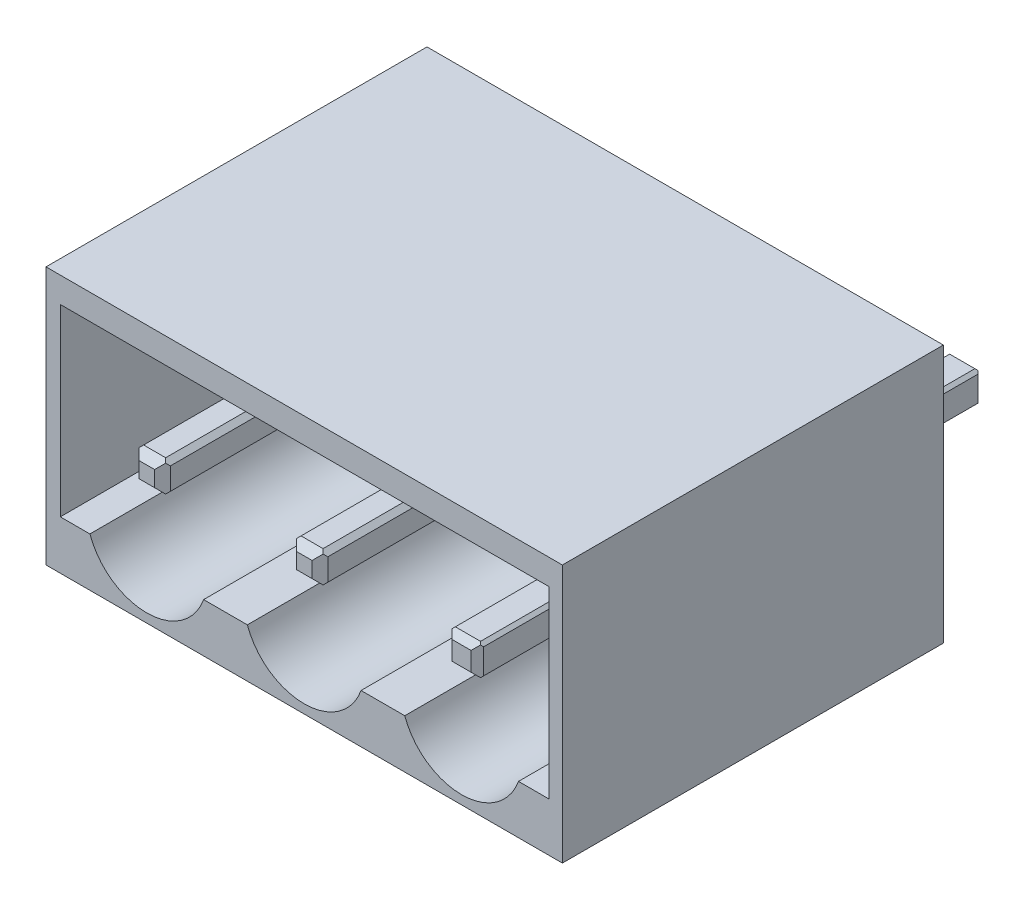
SolidWorks part; units mm, degrees
ref_plane "Спереди" through (0, 0, 0) normal (0, 0, 1) x (1, 0, 0)
ref_plane "Сверху" through (0, 0, 0) normal (0, 1, 0) x (1, 0, 0)
ref_plane "Справа" through (0, 0, 0) normal (1, 0, 0) x (0, 0, -1)
sketch "Эскиз1" plane through (0, 0, 0) normal (0, 0, 1) x (1, 0, 0)
  line L1 (-8.2, 4.1) -> (8.2, 4.1)
  line L2 (-8.2, 4.1) -> (-8.2, -4.1)
  line L3 (-8.2, -4.1) -> (8.2, -4.1)
  line L4 (8.2, 4.1) -> (8.2, -4.1)
  line L5 (-8.2, 4.1) -> (8.2, -4.1) construction
  line L6 (-8.2, -4.1) -> (8.2, 4.1) construction
  point P0 (0, 0)
  dimension "D1" = 8.2
  dimension "D2" = 16.4
extrude "Бобышка-Вытянуть1" add sketch "Эскиз1" along normal blind 12.1
sketch "Эскиз4" plane through (0, 0, 12.1) normal (0, 0, 1) x (1, 0, 0)
  circle A0 centre (-5, 0) radius 1.25
  circle A1 centre (0, 0) radius 1.25
  circle A2 centre (5, 0) radius 1.25
  dimension "D1" = 2.5
  dimension "D2" = 5
  dimension "D3" = 2
  dimension "D4" = 2
extrude "Вырез-Вытянуть3" cut sketch "Эскиз4" against normal blind 8
sketch "Эскиз5" plane through (0, 0, 12.1) normal (0, 0, 1) x (1, 0, 0)
  line L0 (-7.7456, 0) -> (-7.7456, 3.2929)
  line L1 (-7.7456, 3.2929) -> (2.7785, 3.2929)
  line L4 (-7.7456, -2.549) -> (-7.7456, 0)
  line L5 (1.8058, -2.549) -> (3.1942, -2.549)
  line L6 (-6.8058, -2.549) -> (-7.7456, -2.549)
  line L7 (-3.1942, -2.549) -> (-1.8058, -2.549)
  line L9 (6.8058, -2.549) -> (7.7785, -2.549)
  line L10 (7.7785, 3.2929) -> (7.7785, -2.549)
  line L11 (2.7785, 3.2929) -> (7.7785, 3.2929)
  line L13 (1.8058, -2.549) -> (3.1942, -2.549) [skipped]
  arc A1 (3.1942, -2.549) -> (6.8058, -2.549) centre (5, -1.9) ccw
  arc A5 (-6.8058, -2.549) -> (-3.1942, -2.549) centre (-5, -1.9) ccw
  arc A6 (-1.8058, -2.549) -> (1.8058, -2.549) centre (0, -1.9) ccw
  dimension "D1" = 3.2
  dimension "D2" = 2.2
  dimension "D3" = 2
  dimension "D4" = 2
extrude "Вырез-Вытянуть4" cut sketch "Эскиз5" against normal blind 7.8
sketch "Эскиз7" plane through (0, 0, 4.1) normal (0, 0, 1) x (1, 0, 0)
  line L0 (-0.5, 0.5) -> (0.5, 0.5)
  line L1 (-5.5, 0.5) -> (-4.5, 0.5)
  line L2 (-5.5, 0.5) -> (-5.5, -0.5)
  line L3 (-5.5, -0.5) -> (-4.5, -0.5)
  line L4 (-4.5, 0.5) -> (-4.5, -0.5)
  line L5 (-5.5, 0.5) -> (-4.5, -0.5) construction
  line L6 (-5.5, -0.5) -> (-4.5, 0.5) construction
  line L7 (-0.5, 0.5) -> (-0.5, -0.5)
  line L8 (-0.5, -0.5) -> (0.5, -0.5)
  line L9 (0.5, 0.5) -> (0.5, -0.5)
  line L10 (-0.5, 0.5) -> (0.5, -0.5) construction
  line L11 (-0.5, -0.5) -> (0.5, 0.5) construction
  line L12 (4.5, 0.5) -> (5.5, 0.5)
  line L13 (4.5, 0.5) -> (4.5, -0.5)
  line L14 (4.5, -0.5) -> (5.5, -0.5)
  line L15 (5.5, 0.5) -> (5.5, -0.5)
  line L16 (4.5, 0.5) -> (5.5, -0.5) construction
  line L17 (4.5, -0.5) -> (5.5, 0.5) construction
  point P0 (-5, 0)
  point P7 (0, 0)
  point P12 (5, 0)
  dimension "D1" = 1
  dimension "D2" = 1
  dimension "D3" = 2
  dimension "D4" = 2
extrude "Бобышка-Вытянуть2" add sketch "Эскиз7" along normal blind 8
chamfer "Фаска1" distance 0.15 angle 45 8 edges at (-0.5, -0.5, 8.1) (-0.5, 0.5, 8.1) (0.5, 0.5, 8.1) (0.5, -0.5, 8.1) (-4.5, -0.5, 8.1) (-4.5, 0.5, 8.1) (-5.5, -0.5, 8.1) (-5.5, 0.5, 8.1)
chamfer "Фаска2" distance 0.25 angle 45 8 edges at (-0.5, 0, 12.1) (0, 0.5, 12.1) (0.5, 0, 12.1) (0, -0.5, 12.1) (-4.5, 0, 12.1) (-5, -0.5, 12.1) (-5.5, 0, 12.1) (-5, 0.5, 12.1)
sketch "Эскиз8" plane through (0, -4.1, 0) normal (0, 0, 1) x (-1, 0, 0)
  line L0 (0.5, -4.25) -> (-0.5, -4.25)
  line L1 (5.5, -4.25) -> (4.5, -4.25)
  line L2 (5.5, -4.25) -> (5.5, -3.25)
  line L3 (5.5, -3.25) -> (4.5, -3.25)
  line L4 (4.5, -4.25) -> (4.5, -3.25)
  line L5 (5.5, -4.25) -> (4.5, -3.25) construction
  line L6 (5.5, -3.25) -> (4.5, -4.25) construction
  line L7 (0.5, -4.25) -> (0.5, -3.25)
  line L8 (0.5, -3.25) -> (-0.5, -3.25)
  line L9 (-0.5, -4.25) -> (-0.5, -3.25)
  line L10 (0.5, -4.25) -> (-0.5, -3.25) construction
  line L11 (0.5, -3.25) -> (-0.5, -4.25) construction
  line L12 (-4.5, -4.25) -> (-5.5, -4.25)
  line L13 (-4.5, -4.25) -> (-4.5, -3.25)
  line L14 (-4.5, -3.25) -> (-5.5, -3.25)
  line L15 (-5.5, -4.25) -> (-5.5, -3.25)
  line L16 (-4.5, -4.25) -> (-5.5, -3.25) construction
  line L17 (-4.5, -3.25) -> (-5.5, -4.25) construction
  point P0 (5, -3.75)
  point P7 (0, -3.75)
  point P12 (-5, -3.75)
  dimension "D1" = 1
  dimension "D2" = 1
  dimension "D3" = 3.2
  dimension "D4" = 4.45
  dimension "D5" = 2
  dimension "D6" = 2
extrude "Бобышка-Вытянуть3" add sketch "Эскиз8" against normal blind 4
chamfer "Фаска6" distance 0.1 angle 45 4 edges at (4.5, -0.5, 8.1) (5.5, -0.5, 8.1) (5.5, 0.5, 8.1) (4.5, 0.5, 8.1)
chamfer "Фаска7" distance 0.2 angle 45 4 edges at (5.5, 0, 12.1) (5, -0.5, 12.1) (4.5, 0, 12.1) (5, 0.5, 12.1)
chamfer "Фаска10" distance 0.1 angle 45 12 edges at (-5.5, -0.85, -2) (-5.5, 0.15, -2) (-0.5, -0.85, -2) (-0.5, 0.15, -2) (4.5, -0.85, -2) (4.5, 0.15, -2) (-4.5, -0.85, -2) (0.5, -0.85, -2) (5.5, -0.85, -2) (-4.5, 0.15, -2) (0.5, 0.15, -2) (5.5, 0.15, -2)
chamfer "Фаска11" distance 0.2 angle 45 12 edges at (-4.5, -0.35, -4) (-5, 0.15, -4) (-5.5, -0.35, -4) (-5, -0.85, -4) (0, -0.85, -4) (-0.5, -0.35, -4) (0, 0.15, -4) (0.5, -0.35, -4) (4.5, -0.35, -4) (5, 0.15, -4) (5.5, -0.35, -4) (5, -0.85, -4)
